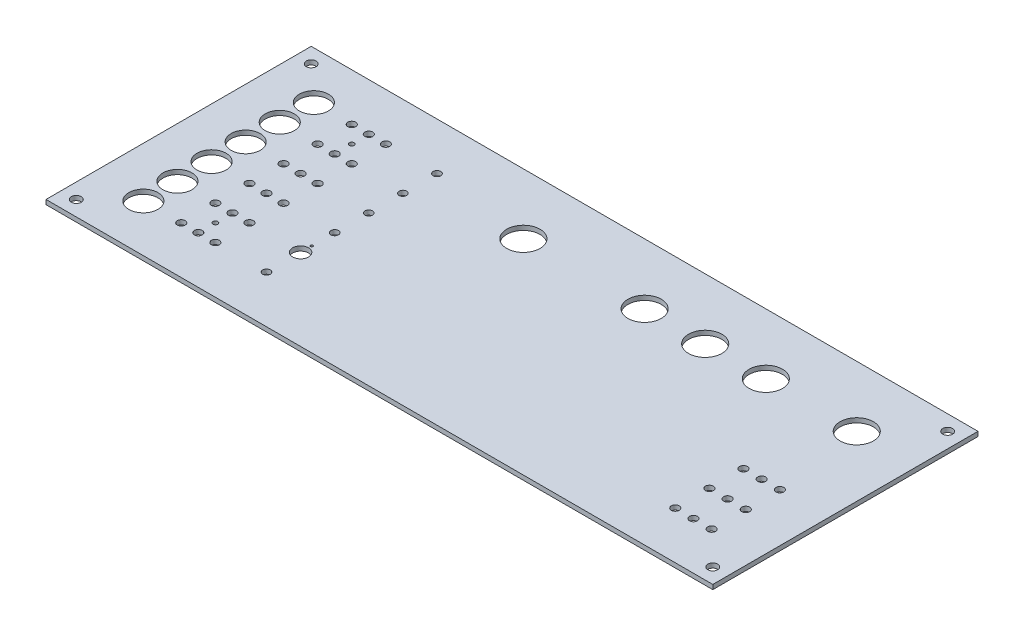
SolidWorks part; units mm, degrees
ref_plane "Front Plane" through (0, 0, 0) normal (0, 0, 1) x (1, 0, 0)
ref_plane "Top Plane" through (0, 0, 0) normal (0, 1, 0) x (1, 0, 0)
ref_plane "Right Plane" through (0, 0, 0) normal (1, 0, 0) x (0, 0, -1)
sketch "Sketch1" plane through (0, 0, 0) normal (0, 1, 0) x (1, 0, 0)
  line L0 (420, 20) -> (20, 20) construction
  line L1 (440, 175) -> (0, 175)
  line L2 (440, 175) -> (440, 0)
  line L3 (440, 0) -> (0, 0)
  line L4 (0, 175) -> (0, 0)
  line L5 (20, 155) -> (20, 20) construction
  line L6 (420, 155) -> (20, 155) construction
  line L7 (420, 155) -> (420, 20) construction
  line L8 (114.25, 20) -> (114.25, 155) construction
  line L9 (20, 143.75) -> (120, 143.75) construction
  line L10 (33, 20) -> (33, 155) construction
  line L11 (20, 121.25) -> (120, 121.25) construction
  line L12 (58, 20) -> (58, 155) construction
  line L13 (120, 98.75) -> (20, 98.75) construction
  line L14 (69.25, 20) -> (69.25, 155) construction
  line L15 (20, 76.25) -> (420, 76.25) construction
  line L16 (80.5, 20) -> (80.5, 155) construction
  line L17 (420, 53.75) -> (20, 53.75) construction
  line L19 (20, 31.25) -> (420, 31.25) construction
  line L20 (420, 135) -> (150, 135) construction
  circle A0 centre (10, 10) radius 3.25
  circle A1 centre (10, 165) radius 3.25
  circle A2 centre (430, 165) radius 3.25
  circle A3 centre (430, 10) radius 3.25
  circle A4 centre (33, 31.25) radius 9.6
  circle A5 centre (33, 53.75) radius 9.6
  circle A6 centre (33, 76.25) radius 9.6
  circle A7 centre (33, 98.75) radius 9.6
  circle A8 centre (33, 121.25) radius 9.6
  circle A9 centre (33, 143.75) radius 9.6
  circle A10 centre (33, 31.25) radius 11 construction
  circle A11 centre (33, 53.75) radius 11 construction
  circle A12 centre (58, 31.25) radius 2.6
  circle A13 centre (58, 53.75) radius 2.6
  circle A14 centre (58, 76.25) radius 2.6
  circle A15 centre (58, 98.75) radius 2.6
  circle A16 centre (58, 121.25) radius 2.6
  circle A17 centre (58, 143.75) radius 2.6
  circle A18 centre (69.25, 31.25) radius 2.6
  circle A19 centre (69.25, 53.75) radius 2.6
  circle A20 centre (69.25, 76.25) radius 2.6
  circle A21 centre (69.25, 98.75) radius 2.6
  circle A22 centre (69.25, 121.25) radius 2.6
  circle A23 centre (69.25, 143.75) radius 2.6
  circle A24 centre (80.5, 31.25) radius 2.6
  circle A25 centre (80.5, 53.75) radius 2.6
  circle A26 centre (80.5, 76.25) radius 2.6
  circle A27 centre (80.5, 98.75) radius 2.6
  circle A28 centre (80.5, 121.25) radius 2.6
  circle A29 centre (80.5, 143.75) radius 2.6
  circle A30 centre (400, 135) radius 11
  circle A31 centre (340, 135) radius 11
  circle A32 centre (300, 135) radius 11
  circle A33 centre (260, 135) radius 11
  circle A34 centre (180, 135) radius 11
  circle A35 centre (408, 31.25) radius 2.6
  circle A36 centre (396, 31.25) radius 2.6
  circle A37 centre (384, 31.25) radius 2.6
  circle A38 centre (408, 53.75) radius 2.6
  circle A39 centre (396, 53.75) radius 2.6
  circle A40 centre (384, 53.75) radius 2.6
  circle A41 centre (408, 76.25) radius 2.6
  circle A42 centre (396, 76.25) radius 2.6
  circle A43 centre (384, 76.25) radius 2.6
  circle A44 centre (114.25, 143.75) radius 2.5
  circle A45 centre (114.25, 121.25) radius 2.5
  circle A46 centre (114.25, 98.75) radius 2.5
  circle A47 centre (114.25, 76.25) radius 2.5
  circle A48 centre (114.25, 53.75) radius 5.25
  circle A49 centre (114.25, 31.25) radius 2.5
  circle A50 centre (114.25, 61.17) radius 0.8
  circle A51 centre (69.25, 132.5) radius 1.6
  circle A52 centre (69.25, 42.5) radius 1.6
  dimension "D1" = 135
  dimension "D3" = 22.5
  dimension "D28" = 10
  dimension "D30" = 10
  dimension "D31" = 10
  dimension "D33" = 260
  dimension "D21" = 10.5
  dimension "D34" = 5.2
  dimension "D35" = 7.42
  dimension "D36" = 1.6
  dimension "D37" = 11.25
  dimension "D38" = 11.25
  dimension "D39" = 3.2
  dimension "D40" = 3.2
  dimension "D42" = 22
  dimension "D64" = 19.2
  dimension "D65" = 6.5
  dimension "D4" = 22.5
  dimension "D5" = 22.5
  dimension "D6" = 22.5
  dimension "D7" = 22.5
  dimension "D8" = 11.25
  dimension "D9" = 11.25
  dimension "D10" = 11.25
  dimension "D11" = 25
  dimension "D12" = 13
  dimension "D13" = 20
  dimension "D14" = 12
  dimension "D15" = 12
  dimension "D16" = 12
  dimension "D17" = 40
  dimension "D18" = 100
  dimension "D19" = 140
  dimension "D20" = 180
  dimension "D22" = 440
  dimension "D23" = 400
  dimension "D24" = 33.75
  dimension "D25" = 10
  dimension "D26" = 10
  dimension "D27" = 10
  dimension "D29" = 10
  dimension "D32" = 10
  dimension "D41" = 175
  dimension "D43" = 40
  dimension "D44" = 98.75
  dimension "D45" = 121.25
  dimension "D46" = 143.75
  dimension "D47" = 31.25
  dimension "D48" = 53.75
  dimension "D49" = 76.25
  dimension "D50" = 32
  dimension "D51" = 44
  dimension "D52" = 56
  dimension "D53" = 31.25
  dimension "D54" = 53.75
  dimension "D55" = 76.25
  dimension "D56" = 98.75
  dimension "D57" = 121.25
  dimension "D58" = 143.75
  dimension "D59" = 114.25
  dimension "D60" = 33
  dimension "D61" = 58
  dimension "D62" = 69.25
  dimension "D63" = 80.5
extrude "Boss-Extrude1" add sketch "Sketch1" along normal blind 3
